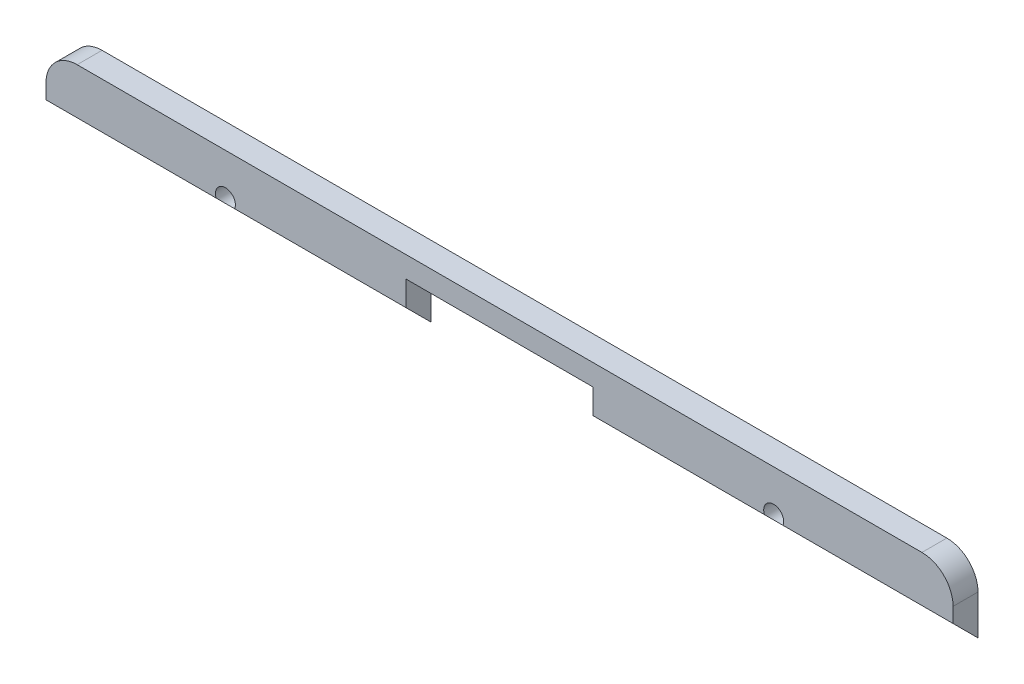
SolidWorks part; units mm, degrees
material "6061-T6 (SS)"
ref_plane "Front Plane" through (0, 0, 0) normal (0, 0, 1) x (1, 0, 0)
ref_plane "Top Plane" through (0, 0, 0) normal (0, 1, 0) x (1, 0, 0)
ref_plane "Right Plane" through (0, 0, 0) normal (1, 0, 0) x (0, 0, -1)
sketch "Sketch1" plane through (0, 0, 0) normal (1, 0, 0) x (0, 0, -1)
  line L0 (-3.0983, 0) -> (1.226, 0) construction
  line L1 (0, -3.2) -> (-2, -1.2)
  line L2 (0, -3.2) -> (0, 3.2)
  line L4 (-2, -1.2) -> (-2, 3.2)
  line L5 (-2, 3.2) -> (0, 3.2)
  dimension "D1" = 2
  dimension "D2" = 45
  dimension "D3" = 6.4
extrude "Boss-Extrude1" add sketch "Sketch1" along normal mid plane 72.8
sketch "Sketch4" plane through (0, 0, 0) normal (0, 0, 1) x (1, 0, 0)
  line L1 (7.5, 1.5) -> (-7.5, 1.5)
  line L2 (7.5, 1.5) -> (7.5, -3.2)
  line L3 (7.5, -3.2) -> (-7.5, -3.2)
  line L4 (-7.5, 1.5) -> (-7.5, -3.2)
  line L5 (0, 7.7759) -> (0, -8.8374) construction
  line L8 (-7.5, -1.7) -> (-7.5, -0.7) construction
  dimension "D1" = 4.7
hole_wizard "M2x0.4 Tapped Hole1" positions "Sketch2" profile "Sketch3" tap size "M2x0.4" standard "ANSI Metric" end condition through all
sketch "Sketch2" plane through (0, 0, 2) normal (0, 0, 1) x (1, 0, 0)
  circle A4 centre (-22, -0.2) radius 1.2 construction
  circle A5 centre (-22, -0.2) radius 1.2
  circle A6 centre (0, -0.2) radius 1.2 construction
  circle A7 centre (0, -0.2) radius 1.2
  circle A8 centre (22, -0.2) radius 1.2 construction
  circle A9 centre (22, -0.2) radius 1.2
  point P22 (-22, -0.2)
  point P25 (0, -0.2)
  point P28 (22, -0.2)
sketch "Sketch3" plane through (-22, -0.2, 2) normal (1, 0, 0) x (0, -1, 0)
  line L0 (0, 0) -> (0, 2)
  line L1 (0, 2) -> (0.8, 2)
  line L2 (0.8, 2) -> (0.8, 0)
  line L5 (0.8, 0) -> (0, 0)
  line L11 (0, -6.35) -> (0, 107.95) construction
  dimension "Thru Tap Drill Dia." = 1.6
  dimension "Thru Tap Drill Depth" = 2
cosmetic thread "Hole Thread4" [suppressed] parameters "D2"=2
cosmetic thread "Hole Thread5" [suppressed] parameters "D2"=2
cosmetic thread "Hole Thread6" [suppressed] parameters "D2"=2
extrude "Cut-Extrude4" cut sketch "Sketch4" along normal through all
fillet "Fillet3" radius 2.5 2 edges at (-36.4, 3.2, 1) (36.4, 3.2, 1)
sketch "Sketch5" [suppressed] plane through (-36.4, 0, 0) normal (-1, 0, 0) x (0, 0, 1)
  line L0 (0, -2.7) -> (2, -0.7)
  line L1 (0, -3.2) -> (0, 0.7) construction
  line L2 (2, 0.7) -> (2, -1.2) construction
  line L3 (2, -1.2) -> (0, -3.2) construction
  line L4 (2, -1.2) -> (2, -0.7)
  line L5 (2, -1.2) -> (0, -3.2)
  line L6 (0, -3.2) -> (0, -2.7)
  dimension "D1" = 0.5
extrude "Cut-Extrude5" [suppressed] cut sketch "Sketch5" against normal up to surface (72.8 mm away) up to face at (36.4, -0.75, 1)
sketch "Sketch6" plane through (-36.4, 0, 0) normal (-1, 0, 0) x (0, 0, 1)
  line L0 (2, -0.4929) -> (0, -2.4929)
  line L1 (2, 0.7) -> (2, -1.2) construction
  line L2 (0, -3.2) -> (0, 0.7) construction
  line L3 (2, -1.2) -> (0, -3.2) construction
  line L4 (2, -0.4929) -> (2, -1.2)
  line L5 (2, -1.2) -> (0, -3.2)
  line L6 (0, -3.2) -> (0, -2.4929)
  dimension "D1" = 0.5
extrude "Cut-Extrude6" cut sketch "Sketch6" against normal up to surface (72.8 mm away) up to face at (36.4, -0.75, 1)
